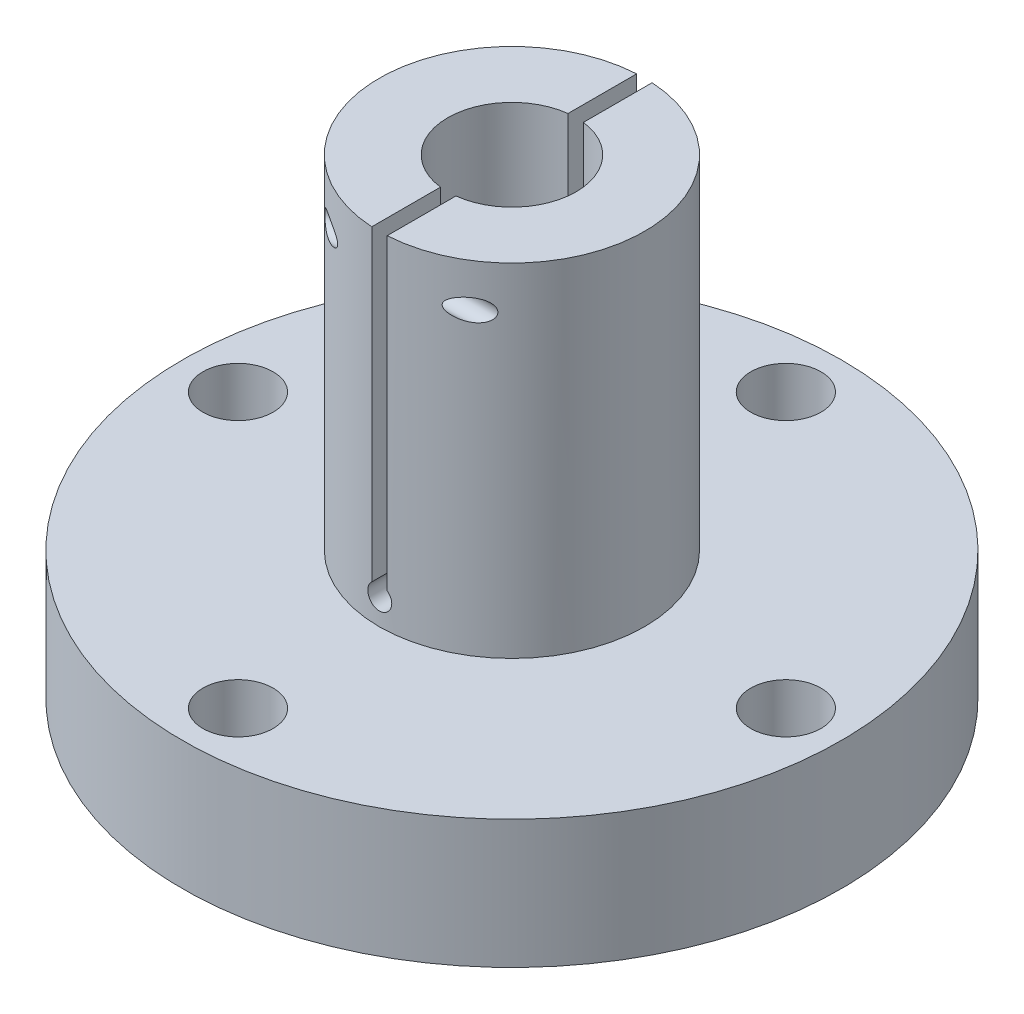
SolidWorks part; units mm, degrees
material "AISI 1045 Steel, cold drawn"
ref_plane "Front Plane" through (0, 0, 0) normal (0, 0, 1) x (1, 0, 0)
ref_plane "Top Plane" through (0, 0, 0) normal (0, 1, 0) x (1, 0, 0)
ref_plane "Right Plane" through (0, 0, 0) normal (1, 0, 0) x (0, 0, -1)
sketch "Sketch1" plane through (0, 0, 0) normal (0, 0, 1) x (1, 0, 0)
  line L0 (0, 0) -> (0, 90.6987) construction
  line L1 (7.5, 55) -> (7.5, 15)
  line L2 (7.5, 15) -> (9, 15)
  line L3 (9, 15) -> (9, 7)
  line L4 (9, 7) -> (25, 7)
  line L5 (25, 7) -> (25, 0)
  line L6 (25, 0) -> (38.5, 0)
  line L7 (38.5, 0) -> (38.5, 15)
  line L8 (38.5, 15) -> (15.5, 15)
  line L9 (15.5, 15) -> (15.5, 55)
  line L10 (15.5, 55) -> (7.5, 55)
  point P5 (0, 0)
  point P14 (0, 0)
  point P15 (0, 0)
  point P16 (0, 0)
  point P17 (0, 0)
  dimension "D1" = 13.5
  dimension "D2" = 25
  dimension "D3" = 8
  dimension "D4" = 9
  dimension "D5" = 7.5
  dimension "D6" = 40
  dimension "D7" = 15
  dimension "D8" = 7
revolve "Revolve1" add sketch "Sketch1" angle 360 about L0
sketch "Sketch2" plane through (0, 0, 0) normal (0, 0, 1) x (1, 0, 0)
  line L0 (38.5, 15) -> (-38.5, 15) construction
  line L1 (-0.9, 55) -> (0.9, 55)
  line L2 (-0.9, 55) -> (-0.9, 19.0724)
  line L4 (0.9, 55) -> (0.9, 19.0724)
  line L5 (-0.9, 55) -> (0.9, 19.0724) construction
  line L6 (-0.9, 19.0724) -> (0.9, 55) construction
  line L8 (7.5, 55) -> (-7.5, 55) construction
  arc A0 (-0.9, 19.0724) -> (0.9, 19.0724) centre (0, 18) ccw
  point P2 (0, 37.0362)
  point P9 (0, 0)
  point P11 (0, 0)
  point P12 (0, 0)
  point P13 (0, 0)
  dimension "D1" = 2.8
  dimension "D3" = 3
  dimension "D2" = 1.8
extrude "Cut-Extrude1" cut sketch "Sketch2" against normal through all both and the other way through all
sketch "Sketch3" plane through (-0.9, 0, 0) normal (1, 0, 0) x (0, 0, -1)
  line L0 (0, 66.094) -> (0, 7.8797) construction
  line L1 (38.5, 15) -> (-38.5, 15) construction
  circle A0 centre (-13, 50) radius 1.25
  circle A1 centre (13, 50) radius 1.25
  dimension "D1" = 2.5
  dimension "D2" = 2.5
  dimension "D5" = 35
  dimension "D3" = 13
  dimension "D4" = 13
extrude "Cut-Extrude2" cut sketch "Sketch3" against normal through all from offset 2.5 offset against normal yes
sketch "Sketch4" plane through (-3.4, 0, 0) normal (-1, 0, 0) x (0, 0, 1)
  circle A0 centre (13, 50) radius 0.5
  circle A1 centre (-13, 50) radius 0.5
  dimension "D1" = 1
  dimension "D2" = 1
extrude "Cut-Extrude3" cut sketch "Sketch4" against normal through all
mirror "Mirror1" about plane through (0, 0, 0) normal (1, 0, 0) of "Cut-Extrude2"
sketch "Sketch5" plane through (0, 0, 0) normal (0, -1, 0) x (1, 0, 0)
  circle A0 centre (32, 0) radius 2.25
  dimension "D1" = 4.5
  dimension "D2" = 32
extrude "Cut-Extrude4" cut sketch "Sketch5" against normal through all
sketch "Sketch6" plane through (0, 15, 0) normal (0, 1, 0) x (1, 0, 0)
  circle A0 centre (32, 0) radius 4.1
  dimension "D1" = 8.2
extrude "Cut-Extrude5" cut sketch "Sketch6" against normal blind 9
ref_axis "Axis1" through (0, 55, 0) along (0, -1, 0)
pattern_circular "CirPattern1" count 4 over 360 about axis through (0, 55, 0) along (0, -1, 0) of "Cut-Extrude4", "Cut-Extrude5"
